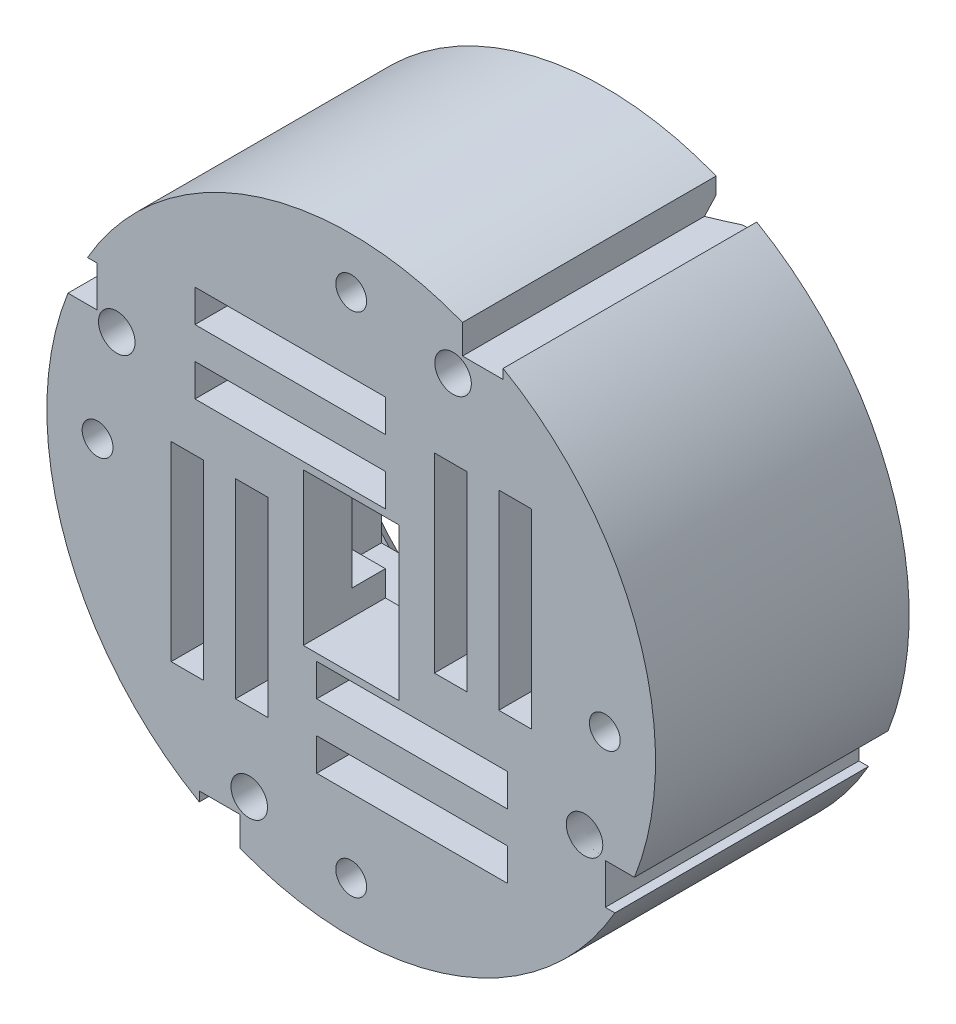
SolidWorks part; units mm, degrees
material "ABS"
ref_plane "Front Plane" through (0, 0, 0) normal (0, 0, 1) x (1, 0, 0)
ref_plane "Top Plane" through (0, 0, 0) normal (0, 1, 0) x (1, 0, 0)
ref_plane "Right Plane" through (0, 0, 0) normal (1, 0, 0) x (0, 0, -1)
sketch "Sketch1" plane through (0, 0, 0) normal (0, 0, 1) x (1, 0, 0)
  circle A0 centre (0, 0) radius 34.29
  circle A1 centre (0, 0) radius 38.1
  dimension "D1" = 76.2
  dimension "D2" = 3.81
extrude "Boss-Extrude1" add sketch "Sketch1" along normal blind 31.75
sketch "Sketch2" plane through (0, 0, 31.75) normal (0, 0, 1) x (1, 0, 0)
  circle A0 centre (0, 0) radius 38.1
  dimension "D1" = 76.2
extrude "Boss-Extrude2" add sketch "Sketch2" against normal blind 21.336
sketch "Sketch3" plane through (0, 0, 31.75) normal (0, 0, 1) x (1, 0, 0)
  line L1 (-6, -9.525) -> (6, -9.525)
  line L2 (-6, -9.525) -> (-6, 9.525)
  line L3 (-6, 9.525) -> (6, 9.525)
  line L4 (6, -9.525) -> (6, 9.525)
  line L5 (-6, -9.525) -> (6, 9.525) construction
  line L6 (-6, 9.525) -> (6, -9.525) construction
  point P0 (0, 0)
  dimension "D1" = 12
  dimension "D2" = 19.05
extrude "Cut-Extrude1" cut sketch "Sketch3" against normal up to surface (21.336 mm away) up to face at (34.29, 0, 10.414)
sketch "Sketch4" plane through (0, 0, 31.75) normal (0, 0, 1) x (1, 0, 0)
  line L1 (10.414, 19.558) -> (14.478, 19.558)
  line L2 (10.414, 19.558) -> (10.414, -4.318)
  line L3 (10.414, -4.318) -> (14.478, -4.318)
  line L4 (14.478, 19.558) -> (14.478, -4.318)
  line L5 (18.478, 19.558) -> (22.542, 19.558)
  line L6 (18.478, 19.558) -> (18.478, -4.318)
  line L7 (18.478, -4.318) -> (22.542, -4.318)
  line L8 (22.542, 19.558) -> (22.542, -4.318)
  line L56 (19.558, -10.414) -> (-4.318, -10.414)
  line L57 (19.558, -10.414) -> (19.558, -14.478)
  line L58 (19.558, -14.478) -> (-4.318, -14.478)
  line L59 (-4.318, -10.414) -> (-4.318, -14.478)
  line L60 (19.558, -18.478) -> (-4.318, -18.478)
  line L61 (19.558, -18.478) -> (19.558, -22.542)
  line L62 (19.558, -22.542) -> (-4.318, -22.542)
  line L63 (-4.318, -18.478) -> (-4.318, -22.542)
  line L64 (-10.414, -19.558) -> (-10.414, 4.318)
  line L65 (-10.414, -19.558) -> (-14.478, -19.558)
  line L66 (-14.478, -19.558) -> (-14.478, 4.318)
  line L67 (-10.414, 4.318) -> (-14.478, 4.318)
  line L68 (-18.478, -19.558) -> (-18.478, 4.318)
  line L69 (-18.478, -19.558) -> (-22.542, -19.558)
  line L70 (-22.542, -19.558) -> (-22.542, 4.318)
  line L71 (-18.478, 4.318) -> (-22.542, 4.318)
  line L72 (-19.558, 10.414) -> (4.318, 10.414)
  line L73 (-19.558, 10.414) -> (-19.558, 14.478)
  line L74 (-19.558, 14.478) -> (4.318, 14.478)
  line L75 (4.318, 10.414) -> (4.318, 14.478)
  line L76 (-19.558, 18.478) -> (4.318, 18.478)
  line L77 (-19.558, 18.478) -> (-19.558, 22.542)
  line L78 (-19.558, 22.542) -> (4.318, 22.542)
  line L79 (4.318, 18.478) -> (4.318, 22.542)
  point P36 (0, 0)
  point P37 (0, 0)
  dimension "D6" = 4
  dimension "D1" = 4.064
  dimension "D2" = 4
  dimension "D3" = 23.876
  dimension "D4" = 4.318
  dimension "D5" = 14.478
extrude "Cut-Extrude2" cut sketch "Sketch4" against normal blind 7.62
sketch "Sketch5" plane through (0, 0, 10.414) normal (0, 0, -1) x (-1, 0, 0)
  line L1 (-12.7, -6.35) -> (31.75, -6.35)
  line L2 (-12.7, -6.35) -> (-12.7, 6.35)
  line L3 (-12.7, 6.35) -> (31.75, 6.35)
  line L4 (31.75, -6.35) -> (31.75, 6.35)
  point P0 (0, 0)
  dimension "D1" = 12.7
  dimension "D2" = 31.75
  dimension "D3" = 6.35
  dimension "D4" = 12.7
extrude "Cut-Extrude3" cut sketch "Sketch5" against normal blind 15.24
sketch "Sketch6" plane through (0, 0, 10.414) normal (0, 0, -1) x (-1, 0, 0)
  line L0 (1.9363, 22.86) -> (25.5583, 22.86)
  line L1 (25.5583, 22.86) -> (25.5583, 9.976)
  line L2 (25.5583, 9.976) -> (28.4973, 9.976)
  line L3 (28.4973, 9.976) -> (28.4973, 8.96)
  line L4 (28.4973, 8.96) -> (25.5583, 8.96)
  line L5 (25.5583, 8.96) -> (25.5583, 6.35)
  line L6 (31.75, 6.35) -> (6, 6.35) construction
  line L7 (25.5583, 6.35) -> (31.75, 6.35)
  line L8 (31.75, 6.35) -> (31.75, -6.35)
  line L9 (31.75, -6.35) -> (-12.7, -6.35)
  line L10 (-12.7, -6.35) -> (-12.7, 6.35)
  line L11 (-12.7, 6.35) -> (1.9363, 6.35)
  line L12 (1.9363, 6.35) -> (1.9363, 8.96)
  line L13 (1.9363, 8.96) -> (-1.0027, 8.96)
  line L14 (-1.0027, 8.96) -> (-1.0027, 9.976)
  line L15 (-1.0027, 9.976) -> (1.9363, 9.976)
  line L16 (1.9363, 9.976) -> (1.9363, 22.86)
  line L17 (1.9363, 6.35) -> (1.9363, 3.81) construction
  line L18 (1.9363, 3.81) -> (25.5583, 3.81) construction
  line L19 (25.5583, 3.81) -> (25.5583, 6.35) construction
  circle A2 centre (0, 0) radius 38.1
  circle A3 centre (0, 0) radius 38.1 construction
  circle A4 centre (0, 0) radius 34.29 construction
  dimension "D1" = 19.05
  dimension "D2" = 23.622
  dimension "D3" = 29.5
  dimension "D4" = 5.15
  dimension "D5" = 2.54
  dimension "D6" = 1.016
extrude "Boss-Extrude3" add sketch "Sketch6" along normal blind 8
sketch "Sketch8" plane through (0, 0, 2.414) normal (0, 0, -1) x (-1, 0, 0)
  line L1 (28.4973, 9.976) -> (25.5583, 9.976) construction
  circle A0 centre (29.3459, 12.77) radius 2.286
  circle A1 centre (0, 0) radius 34.29 construction
  circle A5 centre (12.763, -29.3299) radius 2.286
  circle A7 centre (-12.754, 29.3529) radius 2.286
  circle A8 centre (-29.3369, -12.747) radius 2.286 [skipped]
  point P15 (0.0045, 0.0115)
  dimension "D1" = 4.572
  dimension "D2" = 2.794
  dimension "D3" = 4
extrude "Cut-Extrude4" cut sketch "Sketch8" against normal through all
chamfer "Chamfer1" distance 1.905 angle 45 1 edges at (34.29, 0, 0)
sketch "Sketch9" plane through (0, 0, 2.414) normal (0, 0, -1) x (-1, 0, 0)
  circle A0 centre (0, -31.75) radius 1.9304
  circle A1 centre (-31.75, 0) radius 1.9304
  circle A2 centre (0, 31.75) radius 1.9304
  circle A3 centre (31.75, 0) radius 1.9304
  point P9 (0, 0)
  dimension "D1" = 3.8608
  dimension "D2" = 31.75
  dimension "D3" = 4
extrude "Cut-Extrude5" cut sketch "Sketch9" against normal through all
sketch "Sketch10" plane through (0, 0, 31.75) normal (0, 0, 1) x (1, 0, 0)
  line L0 (-4.318, -14.478) -> (19.558, -14.478) construction
  circle A0 centre (29.21, -12.446) radius 2.286
  dimension "D3" = 4.572
  dimension "D1" = 2.032
  dimension "D2" = 9.652
sketch3d "3DSketch1"
  spline S1 degree 3 poles (29.21, -12.446, 31.75) (28.042, -13.6065, 25.0786) (25.3651, -15.5316, 21.1462) (18.6134, -22.0102, 16.5039) (14.8693, -23.1531, 15.3723) (10.0157, -25.2815, 10.4751) (8.0896, -27.4395, 0) knots 0 0 0 0 0.447008 0.522827 0.758186 1 1 1 1
sweep "Cut-Sweep1" cut profiles "Sketch10" path "3DSketch1"
sketch "Sketch14" plane through (0, 0, 2.414) normal (0, 0, -1) x (-1, 0, 0)
  line L1 (-27.94, -15.24) -> (-20.066, -15.24)
  line L2 (-27.94, -15.24) -> (-27.94, 15.24)
  line L3 (-27.94, 15.24) -> (-20.066, 15.24)
  line L4 (-20.066, -15.24) -> (-20.066, 15.24)
  line L5 (-27.94, -15.24) -> (-20.066, 15.24) construction
  line L6 (-27.94, 15.24) -> (-20.066, -15.24) construction
  circle A0 centre (-31.75, 0) radius 1.9304 construction
  point P0 (-24.003, 0)
  dimension "D3" = 3.81
  dimension "D1" = 7.874
  dimension "D2" = 30.48
extrude "Cut-Extrude6" cut sketch "Sketch14" against normal blind 8.89
sketch "Sketch15" plane through (0, 0, 2.414) normal (0, 0, -1) x (-1, 0, 0)
  line L0 (-12.7, -6.35) -> (31.75, -6.35) construction
  line L1 (1.9363, -6.35) -> (25.5583, -6.35)
  line L2 (1.9363, -6.35) -> (1.9363, -22.86)
  line L3 (1.9363, -22.86) -> (25.5583, -22.86)
  line L4 (25.5583, -6.35) -> (25.5583, -22.86)
  line L5 (1.9363, 8.96) -> (1.9363, 6.35) construction
  line L6 (25.5583, 9.976) -> (25.5583, 22.86) construction
  arc A0 (-13.665, 31.4495) -> (31.4421, 13.6821) centre (0, 0) ccw construction
extrude "Cut-Extrude7" cut sketch "Sketch15" against normal blind 19.05
sketch "Sketch16" plane through (0, 0, 31.75) normal (0, 0, 1) x (1, 0, 0)
  line L0 (-19.558, 18.478) -> (-19.558, 14.478) construction
  line L1 (-36.8924, 13.938) -> (-31.8124, 13.938)
  line L2 (-36.8924, 13.938) -> (-36.8924, 19.018)
  line L3 (-36.8924, 19.018) -> (-31.8124, 19.018)
  line L4 (-31.8124, 13.938) -> (-31.8124, 19.018)
  line L5 (-36.8924, 13.938) -> (-31.8124, 19.018) construction
  line L6 (-36.8924, 19.018) -> (-31.8124, 13.938) construction
  line L7 (13.938, 36.8924) -> (19.018, 36.8924)
  line L8 (13.938, 36.8924) -> (13.938, 31.8124)
  line L9 (13.938, 31.8124) -> (19.018, 31.8124)
  line L10 (19.018, 36.8924) -> (19.018, 31.8124)
  line L11 (36.8924, -13.938) -> (36.8924, -19.018)
  line L12 (36.8924, -13.938) -> (31.8124, -13.938)
  line L13 (31.8124, -13.938) -> (31.8124, -19.018)
  line L14 (36.8924, -19.018) -> (31.8124, -19.018)
  line L15 (-13.938, -36.8924) -> (-19.018, -36.8924)
  line L16 (-13.938, -36.8924) -> (-13.938, -31.8124)
  line L17 (-13.938, -31.8124) -> (-19.018, -31.8124)
  line L18 (-19.018, -36.8924) -> (-19.018, -31.8124)
  circle A0 centre (0, 0) radius 38.1 construction
  point P0 (-34.3524, 16.478)
  point P11 (-19.558, 16.478)
  point P12 (0, 0)
  point P27 (0, 0)
  dimension "D1" = 5.08
  dimension "D2" = 5.08
  dimension "D3" = 4
extrude "Cut-Extrude8" cut sketch "Sketch16" against normal up to next
